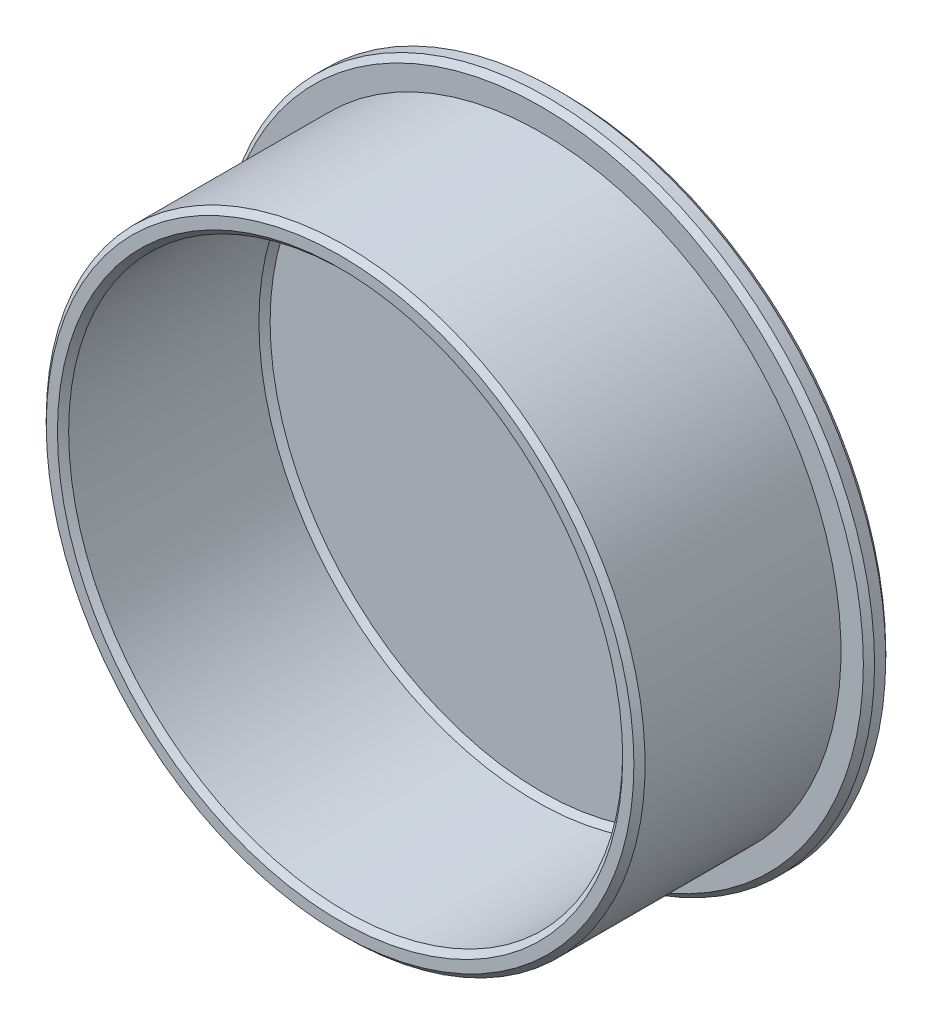
SolidWorks part; units mm, degrees
ref_plane "Front Plane" through (0, 0, 0) normal (0, 0, 1) x (1, 0, 0)
ref_plane "Top Plane" through (0, 0, 0) normal (0, 1, 0) x (1, 0, 0)
ref_plane "Right Plane" through (0, 0, 0) normal (1, 0, 0) x (0, 0, -1)
sketch "Sketch2" plane through (0, 0, 0) normal (0, 0, 1) x (1, 0, 0)
  circle A0 centre (0, 0) radius 29.25
  circle A1 centre (0, 0) radius 26.75
  circle A2 centre (0, 0) radius 24.75
  dimension "D1" = 58.5
  dimension "D2" = 53.5
  dimension "D3" = 2
extrude "Boss-Extrude1" add sketch "Sketch2" along normal blind 2 contours A1 | A0 A1 | A2 region at (-28.4227, 0, 0) region at (-25.9934, 0, 0) region at (0, 0, 0)
extrude "Boss-Extrude2" add sketch "Sketch2<3>" along normal offset from surface (20 mm away) 18 contours A1 region at (-25.9934, 0, 0) up to face at (29.25, 0, 2) offset beyond the face yes
sketch "Sketch2<3>" plane through (0, 0, 0) normal (0, 0, 1) x (1, 0, 0) same geometry as "Sketch2"
chamfer "Chamfer1" distance 0.5 angle 45 5 edges at (29.25, 0, 0) (26.75, 0, 20) (24.75, 0, 20) (29.25, 0, 2) (24.75, 0, 2)
sketch "Sketch3" plane through (0, 0, 0) normal (0, 0, -1) x (-1, 0, 0)
  line L0 (-28.716, -1.397) -> (28.716, -1.397) construction
  line L1 (-27.3804, -8.768) -> (27.3804, -8.768) construction
  circle A0 centre (0, 0) radius 28.75 construction
  text T0 "OpenAstroGuider" font "Roboto" height in points 18
  text T1 "v3.1" font "Roboto" height in points 18
extrude "Cut-Extrude1" [suppressed] cut sketch "Sketch3" against normal blind 0.2
